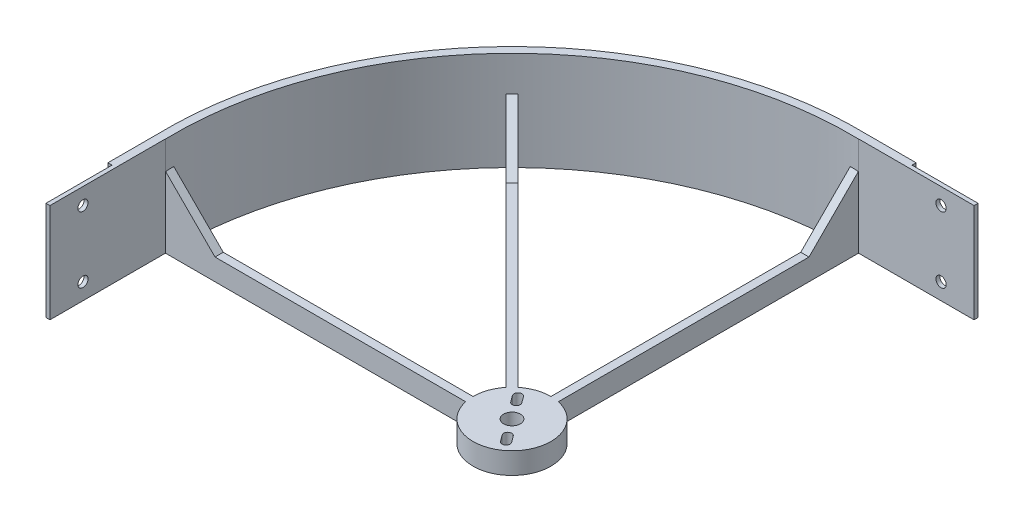
SolidWorks part; units mm, degrees
material "ABS"
ref_plane "Front Plane" through (0, 0, 0) normal (0, 0, 1) x (1, 0, 0)
ref_plane "Top Plane" through (0, 0, 0) normal (0, 1, 0) x (1, 0, 0)
ref_plane "Right Plane" through (0, 0, 0) normal (1, 0, 0) x (0, 0, -1)
sketch "Sketch1" plane through (0, 0, 0) normal (0, 1, 0) x (1, 0, 0)
  line L0 (0, 130.175) -> (0, 9.3426)
  line L1 (3.175, 9.3426) -> (3.175, 130.1363)
  line L2 (0, 0) -> (-22.0351, 22.0351) construction
  line L3 (-22.0351, 22.0351) -> (23.6345, -23.6345) construction
  line L4 (-9.3426, -3.175) -> (-130.1363, -3.175)
  line L5 (-130.175, 0) -> (-9.3426, 0)
  line L6 (3.175, 9.3426) -> (3.175, 130.1363)
  line L7 (3.175, 130.1363) -> (3.175, 133.3122)
  line L8 (-130.1363, -3.175) -> (-133.3122, -3.175)
  line L9 (-93.1633, 90.9182) -> (-10.2883, 8.0432)
  line L10 (-90.9182, 93.1633) -> (-7.1863, 9.4313)
  line L11 (0, 0) -> (-130.175, 0)
  line L12 (-130.175, 0) -> (-129.9364, 0.0546) construction
  line L13 (0, 0) -> (0, 146.05) construction
  circle A0 centre (0, 0) radius 15
  arc A1 (3.175, 130.1363) -> (-130.1363, -3.175) centre (0, 0) ccw
  arc A2 (3.175, 133.3122) -> (-133.3122, -3.175) centre (0, 0) ccw
  point P22 (0, 0)
  dimension "D1" = 30
  dimension "D2" = 133.35
  dimension "D4" = 3.175
  dimension "D3" = 3.175
  dimension "D6" = 1.5875
  dimension "D5" = 1.5875
extrude "Boss-Extrude2" add sketch "Sketch1" along normal blind 8.255 contours A0
extrude "Boss-Extrude3" add sketch "Sketch1<6>" along normal blind 8.255 contours L5 A1 L4 A0 | L6 A1 L0 A0 | A1 A0 region at (1.5882, 0, -72.5246) region at (-51.3161, 0, -51.3161) region at (-72.5246, 0, 1.5882)
sketch "Sketch1<6>" plane through (0, 0, 0) normal (0, 1, 0) x (1, 0, 0) same geometry as "Sketch1"
extrude "Boss-Extrude4" add sketch "Sketch1<7>" along normal blind 38.1 contours L7 A2 L8 A1 region at (-49.8095, 0, -122.3558)
sketch "Sketch1<7>" plane through (0, 0, 0) normal (0, 1, 0) x (1, 0, 0) same geometry as "Sketch1"
ref_plane "Plane1" through (-63.4806, 0, -63.4806) normal (0.7071, 0, 0.7071) x (0.7071, 0, -0.7071)
sketch "Sketch5" plane through (0, 8.255, 0) normal (0, 1, 0) x (1, 0, 0)
  line L0 (0, 0) -> (29.635, 0) construction
  line L1 (0, 0) -> (0, 21.5427) construction
  line L2 (0, 130.175) -> (0, 15) construction
  line L3 (0, 0) -> (29.1655, -1.7838) construction
  line L4 (21.3209, -1.304) -> (-27.7157, 1.6952) construction
  line L5 (0, 0) -> (1.3244, 21.6543) construction
  line L6 (0, 8) -> (0, 0) construction
  line L7 (0, 0) -> (37.8993, -60.1598) construction
  line L8 (0, 0) -> (-19.6346, 0) construction
  line L9 (-130.175, 0) -> (-15, 0) construction
  circle A6 centre (0, 0) radius 3.25
  point P18 (0, 0)
  dimension "D8" = 6.5
  dimension "D2" = 8
  dimension "D5" = 93.5
  dimension "D9" = 90
  dimension "D4" = 57.79
extrude "Cut-Extrude3" cut sketch "Sketch5" against normal blind 63.5
sketch "Sketch6" plane through (0, 0, 3.175) normal (0, 0, 1) x (1, 0, 0)
  line L0 (-14.6601, 0) -> (-133.3122, 0) construction
  line L1 (-130.1363, 38.1) -> (-131.7242, 38.1)
  line L2 (-130.1363, 38.1) -> (-130.1363, 0)
  line L3 (-130.1363, 0) -> (-131.7242, 0)
  line L4 (-131.7242, 38.1) -> (-131.7242, 0)
  line L5 (-130.1363, 38.1) -> (-133.3122, 38.1) construction
  point P7 (-131.7242, 38.1)
sketch "Sketch7" plane through (3.175, 0, 0) normal (1, 0, 0) x (0, 0, -1)
  line L0 (14.6601, 0) -> (133.3122, 0) construction
  line L1 (130.1363, 38.1) -> (131.7242, 38.1)
  line L2 (130.1363, 38.1) -> (130.1363, 0)
  line L3 (130.1363, 0) -> (131.7242, 0)
  line L4 (131.7242, 38.1) -> (131.7242, 0)
  line L5 (130.1363, 38.1) -> (133.3122, 38.1) construction
  line L6 (130.1363, 38.1) -> (130.1363, 8.255) construction
  point P7 (131.7242, 38.1)
ref_plane "Plane3" through (1.1225, 0, -1.1225) normal (0.7071, 0, -0.7071) x (-0.7071, 0, -0.7071)
ref_plane "Plane5" through (0, 0, 0) normal (0, 0, -1) x (-1, 0, 0)
sketch "Sketch14" plane through (0, 0, 0) normal (0, 0, -1) x (-1, 0, 0)
  line L0 (130.175, 8.255) -> (111.125, 8.255)
  line L2 (130.175, 8.255) -> (15, 8.255) construction
  line L5 (130.175, 8.255) -> (130.175, 27.305)
  line L6 (130.175, 8.255) -> (130.175, 38.1) construction
  line L7 (130.175, 27.305) -> (111.125, 8.255)
  dimension "D1" = 19.05
  dimension "D2" = 45
extrude "Boss-Extrude13" add sketch "Sketch14" against normal blind 3.175
ref_plane "Plane6" through (0, 0, 0) normal (-1, 0, 0) x (0, 0, 1)
sketch "Sketch15" plane through (0, 0, 0) normal (-1, 0, 0) x (0, 0, 1)
  line L0 (-130.175, 8.255) -> (-130.175, 27.305)
  line L1 (-130.175, 38.1) -> (-130.175, 8.255) construction
  line L2 (-130.175, 27.305) -> (-111.125, 8.255)
  line L3 (-130.175, 8.255) -> (-15, 8.255) construction
  line L5 (-111.125, 8.255) -> (-130.175, 8.255)
  dimension "D1" = 19.05
  dimension "D2" = 45
extrude "Boss-Extrude14" add sketch "Sketch15" against normal blind 3.175
sketch "Sketch16" plane through (1.1225, 0, -1.1225) normal (0.7071, 0, -0.7071) x (-0.7071, 0, -0.7071)
  line L0 (133.3403, 8.255) -> (111.1153, 8.255)
  line L2 (130.1653, 8.255) -> (14.9158, 8.255) construction
  line L4 (133.3403, 8.255) -> (133.3403, 27.305)
  line L5 (133.3403, 27.305) -> (111.1153, 8.255)
  dimension "D1" = 22.225
  dimension "D2" = 19.05
extrude "Boss-Extrude15" add sketch "Sketch16" against normal blind 3.175
sketch "Sketch17" plane through (0, 8.255, 0) normal (0, 1, 0) x (1, 0, 0)
  line L0 (3.9871, -3.9871) -> (-70.6135, 70.6135) construction
  line L1 (-4.6836, 6.3296) -> (-6.4967, 8.7797) construction
  line L2 (-5.9087, 5.4231) -> (-7.7217, 7.8732)
  line L3 (-3.4586, 7.2361) -> (-5.2716, 9.6862)
  line L4 (0, 0) -> (18.699, 19.3885) construction
  line L5 (-6.4967, 8.7797) -> (0, 0) construction
  line L6 (0, 0) -> (4.11, 3.0412) construction
  line L7 (4.6836, -6.3296) -> (6.4967, -8.7797) construction
  line L8 (3.4586, -7.2361) -> (5.2716, -9.6862)
  line L9 (5.9087, -5.4231) -> (7.7217, -7.8732)
  line L12 (-79.6929, 77.4479) -> (-11.6696, 9.4245) construction
  arc A0 (-5.9087, 5.4231) -> (-3.4586, 7.2361) centre (-4.6836, 6.3296) ccw
  arc A1 (-5.2716, 9.6862) -> (-7.7217, 7.8732) centre (-6.4967, 8.7797) ccw
  arc A2 (3.4586, -7.2361) -> (5.9087, -5.4231) centre (4.6836, -6.3296) cw
  arc A3 (7.7217, -7.8732) -> (5.2716, -9.6862) centre (6.4967, -8.7797) cw
  point P3 (-5.5901, 7.5546)
  point P9 (0, 0)
  point P17 (5.5901, -7.5546)
  dimension "D1" = 7.874
  dimension "D2" = 3.048
  dimension "D3" = 3.048
  dimension "D4" = 8.5
extrude "Cut-Extrude6" cut sketch "Sketch17" against normal through all
ref_plane "Plane7" through (0, 0, -131.7242) normal (0, 0, -1) x (0, -1, 0)
sketch "Sketch20" plane through (0, 0, -131.7242) normal (0, 0, -1) x (0, -1, 0)
  line L0 (-38.1, -3.175) -> (-38.1, -47.625)
  line L1 (-38.1, -47.625) -> (0, -47.625)
  line L2 (0, -47.625) -> (0, -3.175)
  line L3 (0, -3.175) -> (-38.1, -3.175)
  dimension "D1" = 44.45
extrude "Boss-Extrude16" add sketch "Sketch20" against normal blind 1.524
ref_plane "Plane8" through (-131.7242, 0, 0) normal (-1, 0, 0) x (0, -1, 0)
sketch "Sketch21" plane through (-131.7242, 0, 0) normal (-1, 0, 0) x (0, -1, 0)
  line L1 (-38.1, 47.625) -> (0, 47.625)
  line L2 (-38.1, 47.625) -> (-38.1, 3.175)
  line L3 (-38.1, 3.175) -> (0, 3.175)
  line L4 (0, 47.625) -> (0, 3.175)
  dimension "D1" = 44.45
extrude "Boss-Extrude17" add sketch "Sketch21" against normal blind 1.524
sketch "Sketch23" plane through (-131.7242, 0, 0) normal (-1, 0, 0) x (0, 0, 1)
  line L1 (-19.05, 19.05) -> (57.15, 19.05) construction
  line L2 (47.625, 38.1) -> (3.175, 38.1) construction
  line L3 (47.625, 0) -> (47.625, 38.1) construction
  circle A0 centre (34.925, 31.75) radius 1.9431
  circle A1 centre (34.925, 6.35) radius 1.9431
  dimension "D2" = 3.8862
  dimension "D1" = 12.7
  dimension "D3" = 19.05
  dimension "D4" = 12.7
extrude "Cut-Extrude7" cut sketch "Sketch23" against normal blind 2.54
sketch "Sketch24" plane through (0, 0, -131.7242) normal (0, 0, -1) x (-1, 0, 0)
  line L1 (-44.45, 19.05) -> (-3.175, 19.05) construction
  line L2 (-3.175, 0) -> (-3.175, 38.1) construction
  line L3 (-47.625, 38.1) -> (-47.625, 0) construction
  circle A0 centre (-34.925, 31.75) radius 1.985
  circle A1 centre (-34.925, 6.35) radius 1.985
  dimension "D2" = 3.97
  dimension "D1" = 12.7
  dimension "D3" = 12.7
extrude "Cut-Extrude8" cut sketch "Sketch24" against normal blind 2.54
sketch "Sketch25" plane through (-131.7242, 0, 0) normal (-1, 0, 0) x (0, 0, 1)
  line L0 (3.175, 0) -> (47.625, 0) construction
  line L1 (3.175, 38.1) -> (22.225, 38.1)
  line L2 (3.175, 38.1) -> (3.175, 0)
  line L3 (3.175, 0) -> (22.225, 0)
  line L4 (22.225, 38.1) -> (22.225, 0)
  dimension "D1" = 19.05
extrude "Boss-Extrude18" add sketch "Sketch25" along normal up to vertex (1.588 mm away) up to point (-133.3122, 38.1, 3.175)
sketch "Sketch26" plane through (0, 0, -131.7242) normal (0, 0, -1) x (-1, 0, 0)
  line L0 (-47.625, 0) -> (-3.175, 0) construction
  line L1 (-3.175, 38.1) -> (-22.225, 38.1)
  line L2 (-3.175, 38.1) -> (-3.175, 0)
  line L3 (-3.175, 0) -> (-22.225, 0)
  line L4 (-22.225, 38.1) -> (-22.225, 0)
  dimension "D1" = 19.05
extrude "Boss-Extrude19" add sketch "Sketch26" along normal up to vertex (1.588 mm away) up to point (3.175, 38.1, -133.3122)
